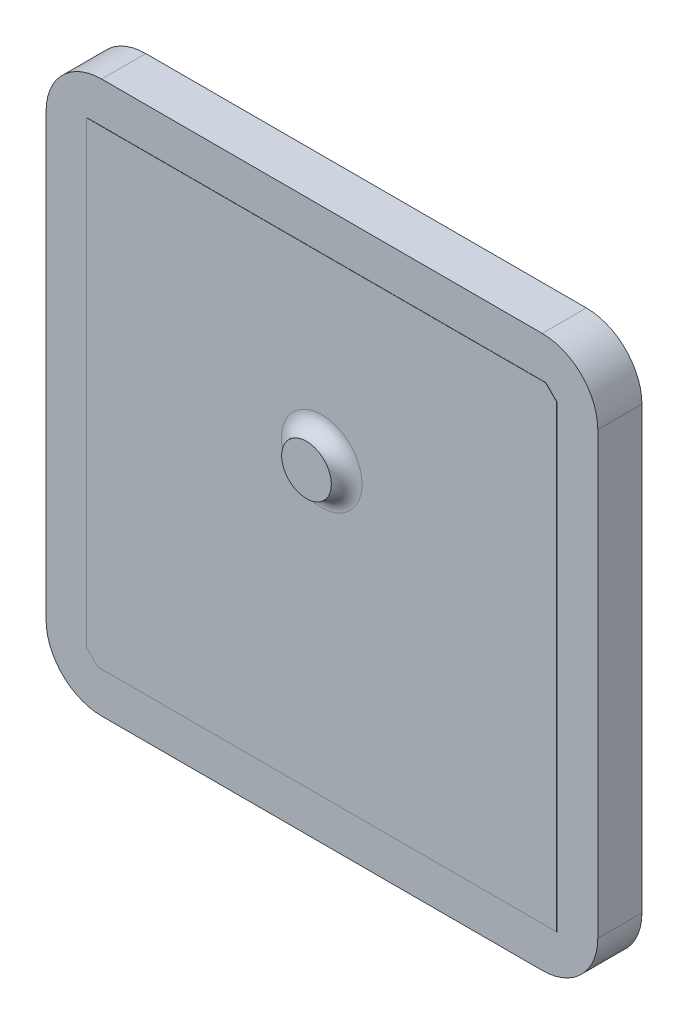
SolidWorks part; units mm, degrees
ref_plane "Front Plane" through (0, 0, 0) normal (0, 0, 1) x (1, 0, 0)
ref_plane "Top Plane" through (0, 0, 0) normal (0, 1, 0) x (1, 0, 0)
ref_plane "Right Plane" through (0, 0, 0) normal (1, 0, 0) x (0, 0, -1)
sketch "Sketch1" plane through (0, 0, 0) normal (0, 0, 1) x (1, 0, 0)
  line L1 (-12.5, 12.5) -> (12.5, 12.5)
  line L2 (-12.5, 12.5) -> (-12.5, -12.5)
  line L3 (-12.5, -12.5) -> (12.5, -12.5)
  line L4 (12.5, 12.5) -> (12.5, -12.5)
  line L5 (-12.5, 12.5) -> (12.5, -12.5) construction
  line L6 (-12.5, -12.5) -> (12.5, 12.5) construction
  point P4 (0, 0)
  dimension "D1" = 25
extrude "Boss-Extrude1" add sketch "Sketch1" along normal blind 2
sketch "Sketch4" plane through (0, 0, 2) normal (0, 0, 1) x (1, 0, 0)
  line L0 (-12.5, -12.5) -> (12.5, -12.5) construction
  line L1 (-12.5, 12.5) -> (-12.5, -12.5) construction
  circle A0 centre (0, 2.5) radius 1.125
  point P5 (0, -12.5)
  point P9 (-12.5, 0)
  dimension "D1" = 2.25
  dimension "D2" = 2.5
extrude "Boss-Extrude3" add sketch "Sketch4" along normal blind 0.7
sketch "Sketch5" plane through (0, 0, 2) normal (0, 0, 1) x (1, 0, 0)
  line L1 (-10.65, 10.65) -> (10.65, 10.65)
  line L2 (-10.65, 10.65) -> (-10.65, -10.65)
  line L3 (-10.65, -10.65) -> (10.65, -10.65)
  line L4 (10.65, 10.65) -> (10.65, -10.65)
  line L5 (-10.65, 10.65) -> (10.65, -10.65) construction
  line L6 (-10.65, -10.65) -> (10.65, 10.65) construction
  line L7 (12.5, -12.5) -> (12.5, 12.5) construction
  point P4 (0, 0)
  point P9 (12.5, 0)
  dimension "D1" = 21.3
extrude "Boss-Extrude4" add sketch "Sketch5" along normal blind 0.01
fillet "Fillet1" radius 0.7 1 edges at (1.125, 2.5, 2.01)
chamfer "Chamfer1" distance 0.5 angle 45 2 edges at (10.65, 10.65, 2.005) (-10.65, -10.65, 2.005)
sketch "Sketch6" plane through (0, 0, 2) normal (0, 0, 1) x (1, 0, 0)
  line L1 (-12.5, -12.5) -> (12.5, -12.5) construction
  line L3 (12.5, -12.5) -> (12.5, 12.5) construction
  line L6 (12.5, 12.5) -> (-12.5, 12.5) construction
  line L8 (-12.5, 12.5) -> (-12.5, -12.5) construction
  line L11 (12.5, 9.9828) -> (12.5, 12.5)
  line L12 (12.5, 12.5) -> (9.9828, 12.5)
  line L13 (-9.9828, 12.5) -> (-12.5, 12.5)
  line L14 (-12.5, 12.5) -> (-12.5, 9.9828)
  line L15 (-12.5, -9.9828) -> (-12.5, -12.5)
  line L16 (-12.5, -12.5) -> (-9.9828, -12.5)
  line L17 (12.5, -9.9828) -> (12.5, -12.5)
  line L18 (12.5, -12.5) -> (9.9828, -12.5)
  arc A0 (-12.5, 9.9828) -> (-9.9828, 12.5) centre (-9.9828, 9.9828) cw
  arc A1 (9.9828, 12.5) -> (12.5, 9.9828) centre (9.9828, 9.9828) cw
  arc A2 (-9.9828, -12.5) -> (-12.5, -9.9828) centre (-9.9828, -9.9828) cw
  arc A3 (9.9828, -12.5) -> (12.5, -9.9828) centre (9.9828, -9.9828) ccw
  point P19 (-11.7627, -11.7627)
  point P28 (11.7627, 11.7627)
  point P30 (11.7627, -11.7627)
  point P32 (-11.7627, 11.7627)
  dimension "D1" = 33.27
  dimension "D2" = 33.27
extrude "Cut-Extrude1" cut sketch "Sketch6" against normal through all
sketch "Sketch7" plane through (0, 0, 0) normal (0, 0, -1) x (-1, 0, 0)
  circle A0 centre (0, 2.5) radius 0.4
  circle A1 centre (0, 2.5) radius 1.125 construction
  dimension "D1" = 0.8
extrude "Boss-Extrude5" add sketch "Sketch7" along normal blind 2
